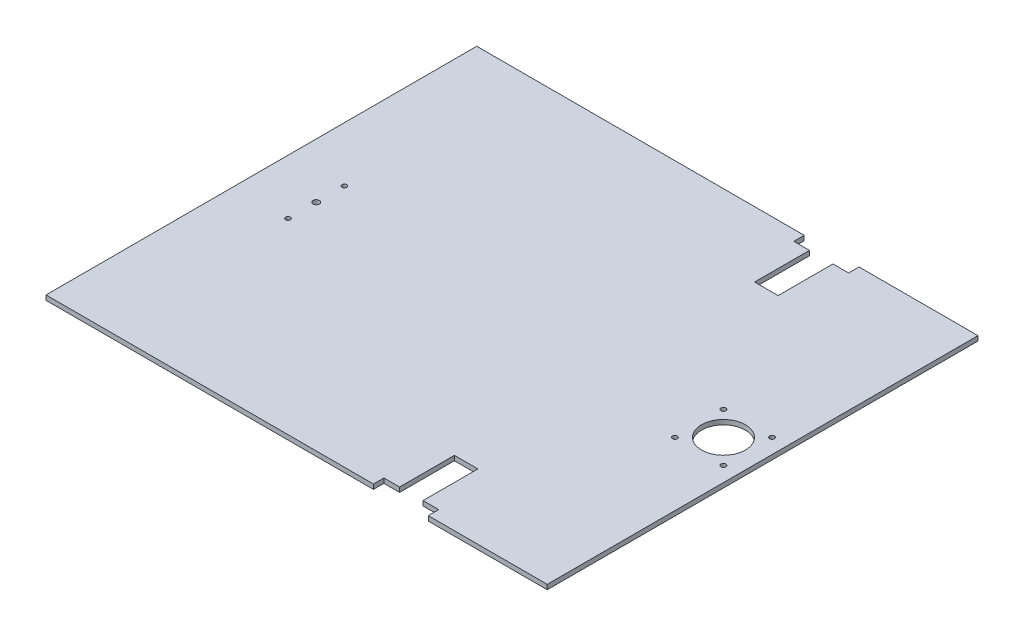
SolidWorks part; units mm, degrees
material "Acrílico (Impacto medio-alto)"
ref_plane "Alzado" through (0, 0, 0) normal (0, 0, 1) x (1, 0, 0)
ref_plane "Planta" through (0, 0, 0) normal (0, 1, 0) x (1, 0, 0)
ref_plane "Vista lateral" through (0, 0, 0) normal (1, 0, 0) x (0, 0, -1)
sketch "Sketch1" plane through (0, 0, 0) normal (0, 1, 0) x (1, 0, 0)
  line L1 (-160, -137.5) -> (160, -137.5)
  line L2 (-160, -137.5) -> (-160, 137.5)
  line L3 (-160, 137.5) -> (160, 137.5)
  line L4 (160, -137.5) -> (160, 137.5)
  line L5 (-160, -137.5) -> (160, 137.5) construction
  line L6 (-160, 137.5) -> (160, -137.5) construction
  point P0 (0, 0)
  dimension "D1" = 320
  dimension "D2" = 275
extrude "Boss-Extrude1" add sketch "Sketch1" along normal blind 3
sketch "Sketch2" plane through (0, 3, 0) normal (0, 1, 0) x (1, 0, 0)
  line L0 (0, 0) -> (160, 0) construction
  line L1 (160, -137.5) -> (160, 137.5) construction
  line L3 (119.5, -15.5) -> (150.5, -15.5)
  line L4 (119.5, -15.5) -> (119.5, 15.5)
  line L5 (119.5, 15.5) -> (150.5, 15.5)
  line L6 (150.5, -15.5) -> (150.5, 15.5)
  line L7 (119.5, -15.5) -> (150.5, 15.5) construction
  line L8 (119.5, 15.5) -> (150.5, -15.5) construction
  point P5 (135, 0)
  dimension "D1" = 31
  dimension "D2" = 31
  dimension "D3" = 25
sketch "Sketch3" plane through (0, 3, 0) normal (0, 1, 0) x (1, 0, 0)
  point P0 (150.5, 15.5)
  point P3 (150.5, -15.5)
  point P6 (119.5, -15.5)
  point P9 (119.5, 15.5)
hole_wizard "Taladro de margen para M2.51" positions "Sketch3" profile "Sketch4" hole size "M2.5" standard "ISO" end condition through all
sketch "Sketch4" plane through (150.5, 3, -15.5) normal (1, 0, 0) x (0, 0, 1)
  line L0 (0, 0) -> (0, 3)
  line L1 (0, 3) -> (1.55, 3)
  line L2 (1.55, 3) -> (1.55, 0)
  line L5 (1.55, 0) -> (0, 0)
  line L11 (0, -6.35) -> (0, 107.95) construction
  dimension "Diámetro de taladro hasta el siguiente" = 3.1
  dimension "Profundidad de taladro hasta el siguiente" = 3
sketch "Sketch6" plane through (0, 3, 0) normal (0, 1, 0) x (1, 0, 0)
  line L0 (0, 0) -> (-160, 0) construction
  line L1 (-160, 137.5) -> (-160, -137.5) construction
  line L2 (-125, 0) -> (-125, 18) construction
  line L3 (-125, 0) -> (-125, -18) construction
  circle A0 centre (-125, -18) radius 1.5
  circle A1 centre (-125, 18) radius 1.5
  dimension "D2" = 3
  dimension "D3" = 3
  dimension "D1" = 36
  dimension "D4" = 35
extrude "Cut-Extrude1" cut sketch "Sketch6" against normal through all
sketch "Sketch7" plane through (0, 3, 0) normal (0, 1, 0) x (1, 0, 0)
  line L0 (119.5, 15.5) -> (150.5, 15.5) construction
  line L1 (135, 15.5) -> (135, 0) construction
  line L2 (150.5, -15.5) -> (150.5, 15.5) construction
  circle A0 centre (135, 0) radius 14
  point P11 (150.5, 0)
  dimension "D1" = 28
extrude "Cut-Extrude2" cut sketch "Sketch7" against normal blind 10
sketch "Sketch8" plane through (0, 3, 0) normal (0, 1, 0) x (1, 0, 0)
  line L0 (-160, -137.5) -> (160, -137.5) construction
  line L1 (84.0517, -137.5) -> (49.0517, -137.5)
  line L2 (84.0517, -137.5) -> (84.0517, -130.8276)
  line L3 (84.0517, -130.8276) -> (74.0517, -130.8276)
  line L4 (49.0517, -137.5) -> (49.0517, -130.8276)
  line L5 (-840, 0) -> (49160, 0) construction
  line L6 (160, -137.5) -> (160, 137.5) construction
  line L7 (84.0517, 137.5) -> (84.0517, 130.8276)
  line L8 (49.0517, 137.5) -> (49.0517, 130.8276)
  line L9 (84.0517, 130.8276) -> (74.0517, 130.8276)
  line L10 (49.0517, 137.5) -> (84.0517, 137.5)
  line L11 (59.0517, 130.8276) -> (49.0517, 130.8276)
  line L13 (74.0517, 130.8276) -> (74.0517, 95.8276)
  line L14 (74.0517, 95.8276) -> (59.0517, 95.8276)
  line L15 (59.0517, 130.8276) -> (59.0517, 95.8276)
  line L16 (74.0517, -95.8276) -> (59.0517, -95.8276)
  line L17 (74.0517, -130.8276) -> (74.0517, -95.8276)
  line L18 (59.0517, -130.8276) -> (59.0517, -95.8276)
  line L19 (59.0517, -130.8276) -> (49.0517, -130.8276)
  line L20 (-125, -18) -> (-125, 0) construction
  circle A0 centre (-125, 0) radius 2
  point P11 (160, 0)
  dimension "D4" = 4
  dimension "D1" = 35
  dimension "D2" = 15
  dimension "D3" = 35
extrude "Cut-Extrude3" cut sketch "Sketch8" against normal blind 10
